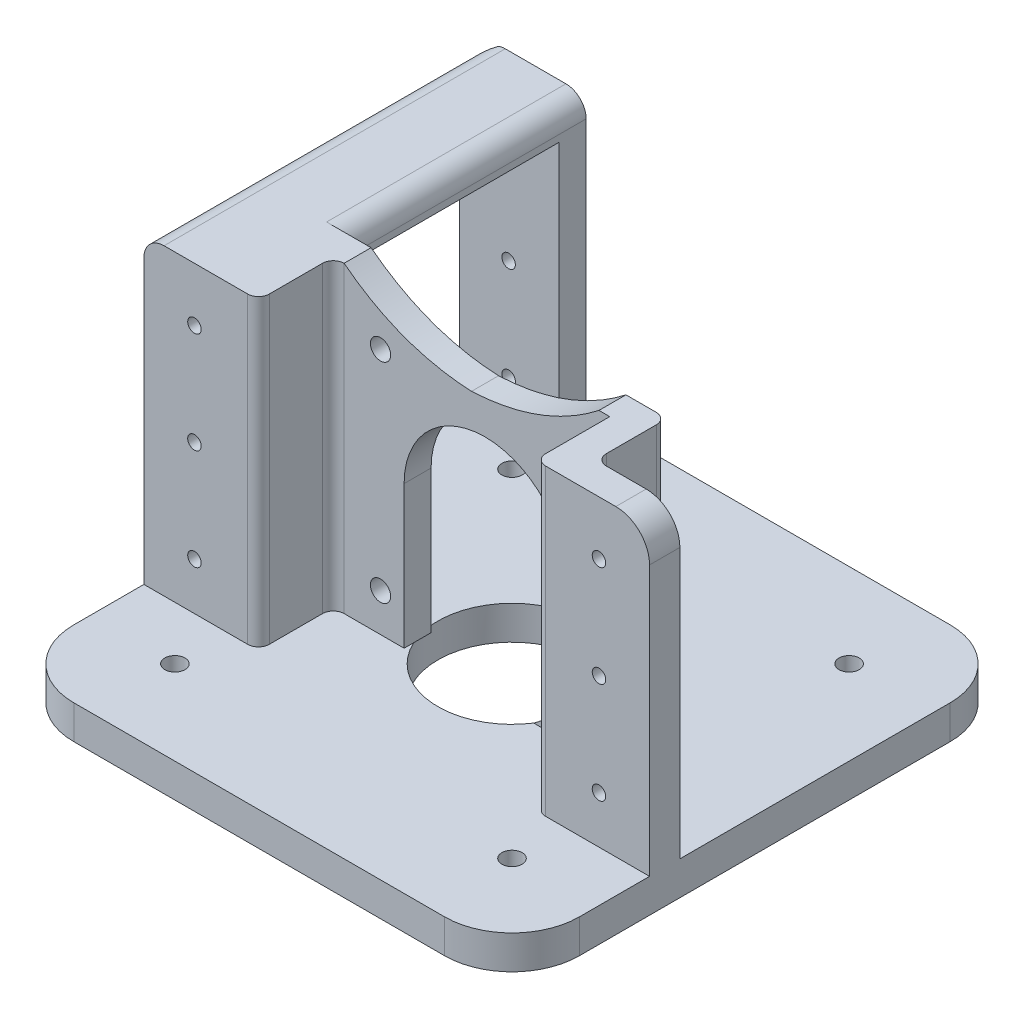
SolidWorks part; units mm, degrees
material "聚脂树脂"
ref_plane "前视基准面" through (0, 0, 0) normal (0, 0, 1) x (1, 0, 0)
ref_plane "上视基准面" through (0, 0, 0) normal (0, 1, 0) x (1, 0, 0)
ref_plane "右视基准面" through (0, 0, 0) normal (1, 0, 0) x (0, 0, -1)
other "Configuration Table"
sketch "草图1" plane through (0, 0, 0) normal (0, 1, 0) x (1, 0, 0)
  line L0 (0, 0) -> (58.6016, 0) construction
  line L1 (-37.5, -37.5) -> (37.5, -37.5)
  line L2 (-37.5, -37.5) -> (-37.5, 37.5)
  line L3 (-37.5, 37.5) -> (37.5, 37.5)
  line L4 (37.5, -37.5) -> (37.5, 37.5)
  line L5 (-37.5, -37.5) -> (37.5, 37.5) construction
  line L6 (-37.5, 37.5) -> (37.5, -37.5) construction
  line L7 (0, 0) -> (0, 47.0411) construction
  line L8 (0, 5) -> (44.8156, 5) construction
  circle A0 centre (0, 0) radius 11
  circle A1 centre (25, 25) radius 1.5
  circle A7 centre (-25, 25) radius 1.5
  circle A8 centre (25, -25) radius 1.5
  circle A9 centre (-25, -25) radius 1.5
  point P0 (0, 0)
  dimension "D3" = 22
  dimension "D4" = 3
  dimension "D7" = 20
  dimension "D8" = 3
  dimension "D10" = 50
  dimension "D1" = 75
  dimension "D2" = 75
  dimension "D5" = 25
  dimension "D6" = 5
  dimension "D9" = 30
extrude "凸台-拉伸1" add sketch "草图1" along normal blind 5
sketch "草图2" plane through (0, 5, 0) normal (0, 1, 0) x (1, 0, 0)
  line L0 (0, 0) -> (55.3583, 0) construction
  line L1 (0, 0) -> (0, 46.1954) construction
  line L2 (0, 0) -> (0, -38.3673) construction
  line L3 (-25, -2) -> (25, -2)
  line L4 (25, -2) -> (25, -12.6)
  line L5 (25, -12.6) -> (37.5, -12.6)
  line L6 (37.5, -12.6) -> (37.5, -17.1)
  line L7 (37.5, -17.1) -> (20.5, -17.1)
  line L8 (20.5, -17.1) -> (20.5, -6)
  line L9 (20.5, -6) -> (-20.5, -6)
  line L10 (-20.5, -17.1) -> (-20.5, -6)
  line L11 (-37.5, -17.1) -> (-20.5, -17.1)
  line L12 (-37.5, -12.6) -> (-37.5, -17.1)
  line L13 (-25, -12.6) -> (-37.5, -12.6)
  line L14 (-25, -2) -> (-25, -12.6)
  line L15 (-37.5, 29.5) -> (-22.5, 29.5)
  line L16 (-37.5, 37.5) -> (-37.5, -37.5) construction
  line L17 (-22.5, 29.5) -> (-22.5, 33.5)
  line L18 (-22.5, 33.5) -> (-37.5, 33.5)
  line L19 (-37.5, 33.5) -> (-37.5, 29.5)
  line L20 (37.5, 37.5) -> (-37.5, 37.5) construction
  point P14 (0, -6)
  point P19 (0, -2)
  dimension "D8" = 4
  dimension "D1" = 25
  dimension "D2" = 10.6
  dimension "D3" = 20.5
  dimension "D4" = 11.1
  dimension "D5" = 17
  dimension "D6" = 2
  dimension "D7" = 4
  dimension "D9" = 4
  dimension "D10" = 15
extrude "凸台-拉伸2" add sketch "草图2" along normal blind 45
sketch "草图3" plane through (0, 0, 6) normal (0, 0, 1) x (1, 0, 0)
  line L0 (0, 0) -> (0, 69.1059) construction
  line L1 (0, 0) -> (57.4199, 0) construction
  line L2 (0, 5) -> (40.8093, 5) construction
  line L3 (-37.5, 5) -> (37.5, 5) construction
  line L4 (2, 26.15) -> (45.791, 26.15) construction
  line L5 (-30, 12) -> (-30, 61.5047) construction
  line L6 (-37.5, 5) -> (-20.5, 5) construction
  line L7 (0, 26.15) -> (49.1021, 26.15) construction
  line L8 (2, 26.15) -> (2, 61.5047) construction
  circle A0 centre (2, 26.15) radius 12
  circle A5 centre (-30, 12) radius 1
  circle A6 centre (-30, 27) radius 1
  circle A7 centre (-30, 42) radius 1
  circle A8 centre (30, 42) radius 1
  circle A9 centre (30, 27) radius 1
  circle A10 centre (30, 12) radius 1
  circle A11 centre (-30, 57) radius 1
  circle A12 centre (30, 57) radius 1
  circle A13 centre (17.5, 41.65) radius 1.5
  circle A14 centre (-13.5, 41.65) radius 1.5
  circle A15 centre (17.5, 10.65) radius 1.5
  circle A16 centre (-13.5, 10.65) radius 1.5
  dimension "D2" = 24
  dimension "D3" = 3
  dimension "D4" = 31
  dimension "D5" = 31
  dimension "D6" = 2
  dimension "D7" = 2
  dimension "D8" = 2
  dimension "D9" = 15
  dimension "D10" = 15
  dimension "D11" = 7
  dimension "D13" = 2
  dimension "D14" = 15
  dimension "D15" = 2
  dimension "D1" = 21.15
  dimension "D12" = 30
extrude "切除-拉伸1" cut sketch "草图3" along normal blind 60 and the other way blind 60
fillet "圆角3" radius 1.6 7 edges at (20.5, 27.5, 17.1) (-20.5, 27.5, 17.1) (-20.5, 27.5, 6) (25, 27.5, 12.6) (25, 27.5, 2) (-25, 27.5, 2) (-25, 27.5, 12.6)
sketch "草图4" plane through (0, 5, 0) normal (0, 1, 0) x (1, 0, 0)
  line L0 (0, 0) -> (50.2662, 0) construction
  line L1 (0, 0) -> (0, 50.3436) construction
  line L2 (33, -23.9509) -> (33, 23.9509) construction
  circle A0 centre (33, 12) radius 1.5
  circle A1 centre (33, 4) radius 1.5
  circle A2 centre (-33, 4) radius 1.5
  circle A3 centre (-33, 12) radius 1.5
  point P11 (33, 0)
  point P17 (-33, 0)
  dimension "D1" = 3
  dimension "D2" = 3
  dimension "D3" = 8
  dimension "D4" = 12
  dimension "D5" = 33
sketch "草图5" plane through (0, 5, 0) normal (0, 1, 0) x (1, 0, 0)
  line L0 (-37.5, 31.5) -> (-37.5, 37.5)
  line L1 (-37.5, 37.5) -> (-37.5, 33.5) construction
  line L2 (-37.5, 37.5) -> (37.5, 37.5)
  line L3 (37.5, 37.5) -> (37.5, 31.5)
  line L4 (37.5, -12.6) -> (37.5, 37.5) construction
  line L5 (37.5, 31.5) -> (-37.5, 31.5)
  dimension "D1" = 6
sketch "草图6" plane through (0, 0, 6) normal (0, 0, 1) x (1, 0, 0)
  line L0 (0, 0) -> (0, 81.7287) construction
  line L1 (18.9, 50) -> (-18.9, 50)
  spline S0 degree 2 poles (-18.9, 50) (-10.5595, 43.5035) (0, 43) knots 0 0 0 1 1 1
  spline S1 degree 2 poles (18.9, 50) (10.5595, 43.5035) (0, 43) knots 0 0 0 1 1 1
  dimension "D1" = 7
  dimension "D2" = 5
  dimension "D3" = 10
extrude "切除-拉伸4" cut sketch "草图6" against normal blind 10
sketch "草图7" plane through (0, 0, 6) normal (0, 0, 1) x (1, 0, 0)
  line L0 (2, -0.1138) -> (2, 56.2062) construction
  line L1 (0, 0) -> (0, 48.2088) construction
  line L2 (2, 5) -> (14, 5)
  line L3 (-18.9, 5) -> (-9.2195, 5) construction
  line L4 (14, 5) -> (14, 26.15)
  line L5 (14, 26.15) -> (-10, 26.15)
  line L6 (-10, 5) -> (-10, 26.15)
  line L7 (2, 5) -> (-10, 5)
  circle A0 centre (2, 26.15) radius 12 construction
  point P11 (2, 26.15)
  dimension "D1" = 12
  dimension "D2" = 2
extrude "切除-拉伸5" cut sketch "草图7" against normal blind 10
fillet "圆角6" radius 10 1 edges at (14, 5, 4)
sketch "草图9" plane through (-37.5, 0, 0) normal (-1, 0, 0) x (0, 0, 1)
  line L0 (12.6, 46) -> (-29.5, 46)
  line L2 (-29.5, 50) -> (-29.5, 5) construction
  line L3 (-29.5, 46) -> (-29.5, 50)
  line L4 (-29.5, 50) -> (12.6, 50)
  line L5 (12.6, 50) -> (12.6, 46)
  line L7 (12.6, 50) -> (12.6, 5) construction
  line L8 (12.6, 50) -> (12.6, 5) construction
  dimension "D2" = 4
extrude "凸台-拉伸3" add sketch "草图9" against normal up to surface (15 mm away) up to face at (-22.5, 27.5, -31.5)
fillet "圆角8" radius 3 2 edges at (-22.5, 50, -15.75) (-37.5, 50, -8.2)
fillet "圆角7" radius 10 4 edges at (37.5, 2.5, -37.5) (37.5, 2.5, 37.5) (-37.5, 2.5, 37.5) (-37.5, 2.5, -37.5)
fillet "圆角9" radius 5 1 edges at (37.5, 50, 14.85)
